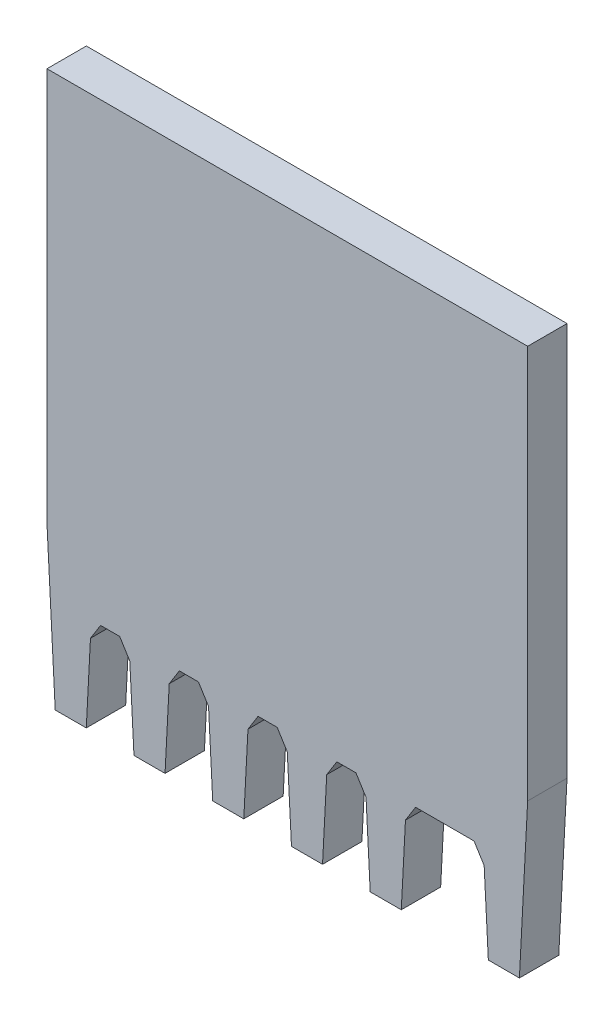
SolidWorks part; units mm, degrees
ref_plane "Front Plane" through (0, 0, 0) normal (0, 0, 1) x (1, 0, 0)
ref_plane "Top Plane" through (0, 0, 0) normal (0, 1, 0) x (1, 0, 0)
ref_plane "Right Plane" through (0, 0, 0) normal (1, 0, 0) x (0, 0, -1)
sketch "Sketch1" plane through (0, 0, 0) normal (0, 0, 1) x (1, 0, 0)
  line L0 (0, 0) -> (0, 21) construction
  line L1 (0, 21) -> (18.3124, 21) construction
  line L2 (18.3124, 21) -> (18.3124, 0) construction
  line L3 (18.3124, 0) -> (0, 0) construction
  line L4 (0, 3) -> (18.3124, 3) construction
  line L5 (0, 6) -> (18.3124, 6) construction
  line L6 (0.9062, 6) -> (0.9062, 0) construction
  line L7 (3.9062, 6) -> (3.9062, 0) construction
  line L8 (6.9062, 6) -> (6.9062, 0) construction
  line L9 (9.9062, 6) -> (9.9062, 0) construction
  line L10 (12.9062, 6) -> (12.9062, 0) construction
  line L11 (17.4062, 6) -> (17.4062, 0) construction
  line L12 (0.9062, 3) -> (3.9062, 3) construction
  line L13 (3.9062, 3) -> (6.9062, 3) construction
  line L14 (6.9062, 3) -> (9.9062, 3) construction
  line L15 (9.9062, 3) -> (12.9062, 3) construction
  line L16 (12.9062, 3) -> (17.4062, 3) construction
  line L17 (0.9062, 3) -> (0, 3) construction
  line L18 (17.4062, 3) -> (18.3124, 3) construction
  line L19 (2.4062, 3) -> (2.4062, 0) construction
  line L20 (5.4062, 3) -> (5.4062, 0) construction
  line L21 (8.4062, 3) -> (8.4062, 0) construction
  line L22 (11.4062, 3) -> (11.4062, 0) construction
  line L23 (15.1562, 3) -> (15.1562, 0) construction
  line L24 (14.4062, 3.75) -> (15.9062, 3.75) construction
  line L25 (0, 6) -> (0.3144, 0)
  line L26 (0.3144, 0) -> (1.4979, 0)
  line L27 (1.4979, 0) -> (1.6572, 3.0393)
  line L28 (3.1552, 3.0393) -> (3.3144, 0)
  line L29 (3.3144, 0) -> (4.4979, 0)
  line L30 (4.4979, 0) -> (4.6572, 3.0393)
  line L31 (6.1552, 3.0393) -> (6.3144, 0)
  line L32 (6.3144, 0) -> (7.4979, 0)
  line L33 (7.4979, 0) -> (7.6572, 3.0393)
  line L34 (9.1552, 3.0393) -> (9.3144, 0)
  line L35 (9.3144, 0) -> (10.4979, 0)
  line L36 (10.4979, 0) -> (10.6572, 3.0393)
  line L37 (12.1552, 3.0393) -> (12.3144, 0)
  line L38 (12.3144, 0) -> (13.4979, 0)
  line L39 (13.4979, 0) -> (13.6572, 3.0393)
  line L40 (16.6552, 3.0393) -> (16.8144, 0)
  line L41 (16.8144, 0) -> (17.9979, 0)
  line L42 (17.9979, 0) -> (18.3124, 6)
  line L44 (1.6572, 3.0393) -> (2.0426, 3.656)
  line L45 (0, 6) -> (0, 21)
  line L46 (0, 21) -> (18.3124, 21)
  line L47 (18.3124, 21) -> (18.3124, 6)
  line L48 (9.1562, 21) -> (9.1562, 6) construction
  line L49 (2.0426, 3.656) -> (2.7698, 3.656)
  line L50 (2.7698, 3.656) -> (3.1552, 3.0393)
  line L51 (4.6572, 3.0393) -> (5.0426, 3.656)
  line L52 (5.0426, 3.656) -> (5.7698, 3.656)
  line L53 (5.7698, 3.656) -> (6.1552, 3.0393)
  line L54 (7.6572, 3.0393) -> (8.0426, 3.656)
  line L55 (8.0426, 3.656) -> (8.7698, 3.656)
  line L56 (8.7698, 3.656) -> (9.1552, 3.0393)
  line L57 (10.6572, 3.0393) -> (11.0426, 3.656)
  line L58 (11.0426, 3.656) -> (11.7698, 3.656)
  line L59 (11.7698, 3.656) -> (12.1552, 3.0393)
  line L60 (13.6572, 3.0393) -> (14.0426, 3.656)
  line L61 (14.0426, 3.656) -> (16.2698, 3.656)
  line L62 (16.2698, 3.656) -> (16.6552, 3.0393)
  arc A0 (3.1552, 3.0393) -> (1.6572, 3.0393) centre (2.4062, 3) ccw construction
  arc A1 (6.1552, 3.0393) -> (4.6572, 3.0393) centre (5.4062, 3) ccw construction
  arc A2 (9.1552, 3.0393) -> (7.6572, 3.0393) centre (8.4062, 3) ccw construction
  arc A3 (12.1552, 3.0393) -> (10.6572, 3.0393) centre (11.4062, 3) ccw construction
  arc A4 (13.6572, 3.0393) -> (14.4062, 3.75) centre (14.4062, 3) cw construction
  arc A5 (16.6552, 3.0393) -> (15.9062, 3.75) centre (15.9062, 3) ccw construction
  dimension "D7" = 0.75
  dimension "D1" = 3
  dimension "D2" = 6
  dimension "D3" = 15
  dimension "D4" = 3
  dimension "D6" = 4.5
  dimension "D8" = 3
  dimension "D9" = 18.3124
  dimension "D10" = 21
extrude "Boss-Extrude1" add sketch "Sketch1" along normal blind 1.5
sketch "Sketch3" plane through (0, 0, 0) normal (0, 0, 1) x (1, 0, 0)
  line L0 (-0.4005, 6) -> (18.7129, 6)
  line L1 (18.7129, 3) -> (-0.4005, 3) construction
  line L2 (-0.4005, 0) -> (18.7129, 0) construction
  line L3 (-0.4005, -0.5) -> (18.7129, -0.5) construction
  line L4 (18.7129, -0.5) -> (18.7129, 6) construction
  line L5 (-0.4005, 6) -> (-0.4005, -0.5) construction
  line L6 (18.3124, 0) -> (0, 0) construction
  line L7 (0, 3) -> (18.3124, 3) construction
  line L8 (0, 6) -> (18.3124, 6) construction
  line L9 (0.3407, -0.5) -> (0, 6) construction
  line L10 (18.3124, 6) -> (17.9717, -0.5) construction
  line L11 (17.9979, 0) -> (18.3124, 6) construction
  line L12 (0, 6) -> (0.3144, 0) construction
  line L13 (5.4062, 6) -> (5.4062, -0.5) construction
  line L14 (3.9062, 6) -> (3.9062, -0.5) construction
  line L15 (5.4062, 3) -> (5.4062, 0) construction
  line L16 (3.1572, 3) -> (3.3407, -0.5) construction
  line L17 (2.7567, 3) -> (2.9401, -0.5)
  line L18 (3.1552, 3.0393) -> (3.3144, 0) construction
  line L19 (2.9401, -0.5) -> (4.8723, -0.5)
  line L20 (4.8723, -0.5) -> (5.0557, 3)
  line L21 (2.8484, 1.25) -> (3.2478, 1.2709) construction
  line L22 (5.9401, -0.5) -> (5.7567, 3)
  line L26 (7.8723, -0.5) -> (5.9401, -0.5)
  line L27 (8.0557, 3) -> (7.8723, -0.5)
  line L30 (2.4062, -0.5) -> (2.4062, 6) construction
  line L31 (2.4062, 3) -> (2.4062, 0) construction
  line L32 (8.4062, 6) -> (8.4062, -0.5) construction
  line L34 (11.4062, -0.5) -> (11.4062, 6) construction
  line L35 (15.1562, -0.5) -> (15.1562, 6) construction
  line L36 (8.4062, 3) -> (8.4062, 0) construction
  line L37 (11.4062, 3) -> (11.4062, 0) construction
  line L38 (15.1562, 3) -> (15.1562, 0) construction
  line L39 (10.8723, -0.5) -> (11.0557, 3)
  line L40 (8.9401, -0.5) -> (10.8723, -0.5)
  line L41 (8.7567, 3) -> (8.9401, -0.5)
  line L42 (11.9401, -0.5) -> (11.7567, 3)
  line L43 (13.8723, -0.5) -> (11.9401, -0.5)
  line L44 (14.0557, 3) -> (13.8723, -0.5)
  line L45 (16.4401, -0.5) -> (18.3723, -0.5)
  line L46 (16.2567, 3) -> (16.4401, -0.5)
  line L47 (18.3723, -0.5) -> (18.7129, 6)
  line L48 (1.8723, -0.5) -> (-0.0599, -0.5)
  line L49 (2.0557, 3) -> (1.8723, -0.5)
  line L50 (-0.0599, -0.5) -> (-0.4005, 6)
  line L51 (16.2567, 3) -> (14.0557, 3)
  line L52 (11.7567, 3) -> (11.0557, 3)
  line L53 (8.7567, 3) -> (8.0557, 3)
  line L54 (5.7567, 3) -> (5.0557, 3)
  line L55 (2.7567, 3) -> (2.0557, 3)
  dimension "D1" = 0.5
  dimension "D2" = 0.4
ref_plane "Plane1" through (3.9062, 0, 0) normal (1, 0, 0) x (0, 0, -1)
sketch "Sketch4" plane through (3.9062, 0, 0) normal (1, 0, 0) x (0, 0, -1)
  line L0 (0, 6) -> (0, -0.5) construction
  line L1 (0.6, 6) -> (-2.1, 6) construction
  line L2 (0.6, 6) -> (0.6, -0.5) construction
  line L3 (0.6, -0.5) -> (-2.1, -0.5) construction
  line L4 (-2.1, 6) -> (-2.1, -0.5) construction
  line L5 (-0.75, -0.5) -> (-0.75, 6) construction
  line L6 (-1.5, 6) -> (-1.5, -0.5) construction
  line L7 (0.6, 2.4005) -> (-2.1, 2.4005) construction
  line L8 (0.3, 6) -> (0.3, -0.5) construction
  line L9 (0.6, 2.4005) -> (3.846, 6) construction
  line L10 (2.2302, 6) -> (0.6, 4.1923) construction
  line L11 (0.6, 4.1923) -> (1.7139, 3.1878) construction
  line L12 (1.7139, 3.1878) -> (4.25, 6)
  line L13 (4.25, 6) -> (0.6, 6) construction
  line L14 (0.3, 1) -> (-1.8, 1) construction
  line L15 (-2.1, 0) -> (0.6, 0) construction
  line L16 (1.7139, 3.1878) -> (1.4912, 3.3887)
  line L17 (1.4912, 3.3887) -> (0.6, 2.4005)
  line L18 (-3.2139, 3.1878) -> (-5.75, 6)
  line L19 (-3.2139, 3.1878) -> (-2.9912, 3.3887)
  line L20 (-2.9912, 3.3887) -> (-2.1, 2.4005)
  line L21 (-2.1, 6) -> (-5.75, 6) construction
  line L22 (0.6, 3.0724) -> (3.2401, 6) construction
  arc A0 (0.4965, 2.2224) -> (0.6, -0.5) centre (4.2, 1) ccw
  arc A1 (0.6, 2.4005) -> (0.4965, 2.2224) centre (0.9713, 2.0656) ccw
  arc A2 (-2.1, 2.4005) -> (-1.9965, 2.2224) centre (-2.4713, 2.0656) cw
  arc A3 (-1.9965, 2.2224) -> (-2.1, -0.5) centre (-5.7, 1) cw
  dimension "D6" = 0.5
  dimension "D1" = 0.6
  dimension "D2" = 0.3
  dimension "D3" = 1.5
  dimension "D4" = 1
  dimension "D5" = 0.3
  dimension "D7" = 10
sketch "Sketch5" plane through (0, 0, 0) normal (1, 0, 0) x (0, 0, -1)
  line L0 (2.2302, 6) -> (0.6, 4.1923) construction
  line L1 (0.6, 4.1923) -> (1.7139, 3.1878) construction
  line L2 (1.7139, 3.1878) -> (4.25, 6) construction
  line L3 (2.2302, 6) -> (0.6, 4.1923) construction
  line L4 (0.6, 4.1923) -> (1.7139, 3.1878) construction
  line L5 (1.7139, 3.1878) -> (4.25, 6) construction
ref_plane "Plane2" through (0, 2.6105, -2.3541) normal (0, 0.7426, -0.6697) x (1, 0, 0)
sketch "Sketch6" plane through (0, 2.6105, -2.3541) normal (0, 0.7426, -0.6697) x (1, 0, 0)
  line L1 (3.9062, -2.362) -> (3.9062, -0.862) construction
  line L2 (3.9062, -2.362) -> (3.9062, -5.0612) construction
  line L3 (4.6562, -5.0612) -> (3.1562, -5.0612)
  line L4 (4.6562, -1.612) -> (3.1562, -1.612) construction
  line L5 (3.1562, -1.612) -> (3.1562, -5.0612)
  line L6 (4.6562, -1.612) -> (4.6562, -5.0612)
  line L10 (2.4062, -5.0612) -> (15.1562, -5.0612) construction
  line L11 (15.1562, -5.0612) -> (15.1562, -0.862) construction
  line L12 (15.1562, -0.862) -> (2.4062, -0.862) construction
  line L13 (2.4062, -0.862) -> (2.4062, -5.0612) construction
  line L14 (15.1562, 0.3349) -> (15.1562, -4.0182) construction
  line L15 (2.4062, 0.3349) -> (2.4062, -4.0182) construction
  line L16 (11.4062, -5.0612) -> (11.4062, -0.862) construction
  line L17 (8.4062, -5.0612) -> (8.4062, -0.862) construction
  line L18 (5.4062, -5.0612) -> (5.4062, -0.862) construction
  line L19 (5.4062, -4.0182) -> (5.4062, 0.3349) construction
  line L20 (8.4062, -4.0182) -> (8.4062, 0.3349) construction
  line L21 (11.4062, 0.3349) -> (11.4062, -4.0182) construction
  line L22 (0.1562, -1.612) -> (0.1562, -5.0612)
  line L23 (0.1562, -5.0612) -> (1.6562, -5.0612)
  line L24 (1.6562, -1.612) -> (1.6562, -5.0612)
  line L25 (7.6562, -1.612) -> (7.6562, -5.0612)
  line L26 (6.1562, -5.0612) -> (7.6562, -5.0612)
  line L27 (6.1562, -1.612) -> (6.1562, -5.0612)
  line L28 (10.6562, -1.612) -> (10.6562, -5.0612)
  line L29 (10.6562, -5.0612) -> (9.1562, -5.0612)
  line L30 (9.1562, -1.612) -> (9.1562, -5.0612)
  line L31 (13.6562, -1.612) -> (13.6562, -5.0612)
  line L32 (12.1562, -5.0612) -> (13.6562, -5.0612)
  line L33 (12.1562, -1.612) -> (12.1562, -5.0612)
  line L34 (18.1562, -1.612) -> (18.1562, -5.0612)
  line L35 (18.1562, -5.0612) -> (16.6562, -5.0612)
  line L36 (16.6562, -1.612) -> (16.6562, -5.0612)
  circle A0 centre (3.9062, -1.612) radius 0.75 construction
  arc A1 (4.6562, -1.612) -> (3.1562, -1.612) centre (3.9062, -1.612) ccw
  arc A2 (0.1562, -1.612) -> (1.6562, -1.612) centre (0.9062, -1.612) cw
  arc A3 (6.1562, -1.612) -> (7.6562, -1.612) centre (6.9062, -1.612) cw
  arc A4 (10.6562, -1.612) -> (9.1562, -1.612) centre (9.9062, -1.612) ccw
  arc A5 (12.1562, -1.612) -> (13.6562, -1.612) centre (12.9062, -1.612) cw
  arc A6 (18.1562, -1.612) -> (16.6562, -1.612) centre (17.4062, -1.612) ccw
ref_plane "Plane3" through (0, 1.6223, -1.463) normal (0, 0.7426, -0.6697) x (1, 0, 0)
sketch "Sketch7" plane through (0, 1.6223, -1.463) normal (0, 0.7426, -0.6697) x (1, 0, 0)
  line L0 (3.1562, -1.612) -> (3.1562, -5.0612) construction
  line L1 (4.6562, -5.0612) -> (3.1562, -5.0612) construction
  line L2 (4.6562, -1.612) -> (4.6562, -5.0612) construction
  line L3 (3.1562, -1.612) -> (3.1562, -5.0612) construction
  line L4 (4.6562, -5.0612) -> (3.1562, -5.0612) construction
  line L5 (4.6562, -1.612) -> (4.6562, -5.0612) construction
  line L6 (3.9062, -0.862) -> (3.9062, -5.0612) construction
  line L7 (4.6562, -1.612) -> (3.1562, -1.612) construction
  line L8 (4.6562, -2.362) -> (3.1562, -2.362) construction
  line L9 (3.4562, -1.612) -> (3.4562, -2.362)
  line L10 (3.4562, -2.362) -> (4.3562, -2.362)
  line L11 (4.3562, -2.362) -> (4.3562, -1.612)
  line L12 (2.4062, -0.862) -> (2.4062, -5.0612) construction
  line L13 (2.4062, -5.0612) -> (15.1562, -5.0612) construction
  line L14 (15.1562, -0.862) -> (2.4062, -0.862) construction
  line L15 (5.4062, -5.0612) -> (5.4062, -0.862) construction
  line L16 (8.4062, -5.0612) -> (8.4062, -0.862) construction
  line L17 (11.4062, -5.0612) -> (11.4062, -0.862) construction
  line L18 (15.1562, -5.0612) -> (15.1562, -0.862) construction
  line L19 (2.4062, -0.862) -> (2.4062, -5.0612) construction
  line L20 (2.4062, -5.0612) -> (15.1562, -5.0612) construction
  line L21 (15.1562, -0.862) -> (2.4062, -0.862) construction
  line L22 (5.4062, -5.0612) -> (5.4062, -0.862) construction
  line L23 (8.4062, -5.0612) -> (8.4062, -0.862) construction
  line L24 (11.4062, -5.0612) -> (11.4062, -0.862) construction
  line L25 (15.1562, -5.0612) -> (15.1562, -0.862) construction
  line L26 (0.4562, -2.362) -> (0.4562, -1.612)
  line L27 (1.3562, -2.362) -> (0.4562, -2.362)
  line L28 (1.3562, -1.612) -> (1.3562, -2.362)
  line L29 (7.3562, -2.362) -> (6.4562, -2.362)
  line L30 (7.3562, -1.612) -> (7.3562, -2.362)
  line L31 (6.4562, -2.362) -> (6.4562, -1.612)
  line L32 (9.4562, -1.612) -> (9.4562, -2.362)
  line L33 (10.3562, -2.362) -> (10.3562, -1.612)
  line L34 (9.4562, -2.362) -> (10.3562, -2.362)
  line L35 (13.3562, -1.612) -> (13.3562, -2.362)
  line L36 (12.4562, -2.362) -> (12.4562, -1.612)
  line L37 (13.3562, -2.362) -> (12.4562, -2.362)
  line L38 (16.9562, -1.612) -> (16.9562, -2.362)
  line L39 (17.8562, -2.362) -> (17.8562, -1.612)
  line L40 (16.9562, -2.362) -> (17.8562, -2.362)
  arc A0 (4.6562, -1.612) -> (3.1562, -1.612) centre (3.9062, -1.612) ccw construction
  arc A1 (4.6562, -1.612) -> (3.1562, -1.612) centre (3.9062, -1.612) ccw construction
  circle A2 centre (3.9062, -1.612) radius 0.45 construction
  arc A3 (4.3562, -1.612) -> (3.4562, -1.612) centre (3.9062, -1.612) ccw
  arc A4 (0.4562, -1.612) -> (1.3562, -1.612) centre (0.9062, -1.612) cw
  arc A5 (6.4562, -1.612) -> (7.3562, -1.612) centre (6.9062, -1.612) cw
  arc A6 (10.3562, -1.612) -> (9.4562, -1.612) centre (9.9062, -1.612) ccw
  arc A7 (12.4562, -1.612) -> (13.3562, -1.612) centre (12.9062, -1.612) cw
  arc A8 (17.8562, -1.612) -> (16.9562, -1.612) centre (17.4062, -1.612) ccw
ref_plane "bisect" through (0, 0, 0.75) normal (0, 0, 1) x (1, 0, 0)
ref_plane "insert_surface" through (0, 6, 0) normal (0, 1, 0) x (1, 0, 0)
sketch "Sketch8" plane through (0, 6, 0) normal (0, 1, 0) x (1, 0, 0)
  line L0 (18.7129, -0.75) -> (-0.4005, -0.75) construction
  line L1 (-0.4005, 0.6) -> (18.7129, 0.6)
  line L2 (-0.4005, 0.6) -> (-0.4005, -2.1)
  line L3 (-0.4005, -2.1) -> (18.7129, -2.1)
  line L4 (18.7129, 0.6) -> (18.7129, -2.1)
  line L5 (9.1562, 0.6) -> (9.1562, -2.1) construction
  line L6 (0, 0) -> (18.3124, 0) construction
  line L7 (0, 0) -> (0, -1.5) construction
  line L8 (0, -1.5) -> (18.3124, -1.5) construction
  line L9 (18.3124, 0) -> (18.3124, -1.5) construction
  line L10 (18.7129, 0.3) -> (-0.4005, 0.3) construction
  line L11 (18.7129, -1.8) -> (-0.4005, -1.8) construction
sketch "Sketch9" plane through (0, 0, 0) normal (0, 0, 1) x (1, 0, 0)
  line L0 (18.3723, -0.5) -> (18.7129, 6) construction
  line L1 (-0.4005, 6) -> (18.7129, 6) construction
  line L2 (-0.0599, -0.5) -> (-0.4005, 6) construction
  line L3 (1.8723, -0.5) -> (-0.0599, -0.5) construction
  line L4 (2.0557, 3) -> (1.8723, -0.5) construction
  line L5 (2.7567, 3) -> (2.0557, 3) construction
  line L6 (2.7567, 3) -> (2.9401, -0.5) construction
  line L7 (2.9401, -0.5) -> (4.8723, -0.5) construction
  line L8 (4.8723, -0.5) -> (5.0557, 3) construction
  line L9 (5.7567, 3) -> (5.0557, 3) construction
  line L10 (5.9401, -0.5) -> (5.7567, 3) construction
  line L11 (7.8723, -0.5) -> (5.9401, -0.5) construction
  line L12 (8.0557, 3) -> (7.8723, -0.5) construction
  line L13 (8.7567, 3) -> (8.0557, 3) construction
  line L14 (8.7567, 3) -> (8.9401, -0.5) construction
  line L15 (8.9401, -0.5) -> (10.8723, -0.5) construction
  line L16 (10.8723, -0.5) -> (11.0557, 3) construction
  line L17 (11.7567, 3) -> (11.0557, 3) construction
  line L18 (11.9401, -0.5) -> (11.7567, 3) construction
  line L19 (13.8723, -0.5) -> (11.9401, -0.5) construction
  line L20 (14.0557, 3) -> (13.8723, -0.5) construction
  line L21 (16.2567, 3) -> (14.0557, 3) construction
  line L22 (16.2567, 3) -> (16.4401, -0.5) construction
  line L23 (16.4401, -0.5) -> (18.3723, -0.5) construction
  line L24 (18.3723, -0.5) -> (18.7129, 6)
  line L25 (-0.4005, 6) -> (18.7129, 6) construction
  line L26 (-0.0599, -0.5) -> (-0.4005, 6)
  line L27 (1.8723, -0.5) -> (-0.0599, -0.5)
  line L28 (2.0557, 3) -> (1.8723, -0.5)
  line L29 (2.7567, 3) -> (2.0557, 3) construction
  line L30 (2.7567, 3) -> (2.9401, -0.5)
  line L31 (2.9401, -0.5) -> (4.8723, -0.5)
  line L32 (4.8723, -0.5) -> (5.0557, 3)
  line L33 (5.7567, 3) -> (5.0557, 3) construction
  line L34 (5.9401, -0.5) -> (5.7567, 3)
  line L35 (7.8723, -0.5) -> (5.9401, -0.5)
  line L36 (8.0557, 3) -> (7.8723, -0.5)
  line L37 (8.7567, 3) -> (8.0557, 3) construction
  line L38 (8.7567, 3) -> (8.9401, -0.5)
  line L39 (8.9401, -0.5) -> (10.8723, -0.5)
  line L40 (10.8723, -0.5) -> (11.0557, 3)
  line L41 (11.7567, 3) -> (11.0557, 3) construction
  line L42 (11.9401, -0.5) -> (11.7567, 3)
  line L43 (13.8723, -0.5) -> (11.9401, -0.5)
  line L44 (14.0557, 3) -> (13.8723, -0.5)
  line L45 (16.2567, 3) -> (14.0557, 3) construction
  line L46 (16.2567, 3) -> (16.4401, -0.5)
  line L47 (16.4401, -0.5) -> (18.3723, -0.5)
  line L48 (16.2567, 3) -> (16.2567, 6)
  line L49 (14.0557, 3) -> (14.0557, 6)
  line L50 (11.7567, 3) -> (11.7567, 6)
  line L51 (18.7129, 6) -> (-0.4005, 6) construction
  line L52 (11.0557, 3) -> (11.0557, 6)
  line L53 (-0.4005, 6) -> (18.7129, 6) construction
  line L54 (8.7567, 3) -> (8.7567, 6)
  line L55 (8.0557, 3) -> (8.0557, 6)
  line L58 (5.7567, 3) -> (5.7567, 6)
  line L60 (5.0557, 3) -> (5.0557, 6)
  line L62 (15.1562, -0.5) -> (15.1562, 6) construction
  line L63 (15.1562, -0.5) -> (15.1562, 6) construction
  line L64 (2.7567, 3) -> (2.7567, 6)
  line L65 (2.0557, 3) -> (2.0557, 6)
  line L67 (18.7129, 6) -> (16.2567, 6)
  line L68 (14.0557, 6) -> (11.7567, 6)
  line L69 (11.0557, 6) -> (8.7567, 6)
  line L70 (8.0557, 6) -> (5.7567, 6)
  line L71 (5.0557, 6) -> (2.7567, 6)
  line L72 (2.0557, 6) -> (-0.4005, 6)
sketch "rgb_led" plane through (0, 0, 1.5) normal (0, 0, 1) x (1, 0, 0)
  line L0 (18.3124, 18) -> (0, 18) construction
  line L1 (18.3124, 6) -> (18.3124, 21) construction
  line L2 (0, 21) -> (0, 6) construction
  line L3 (9.1562, 21) -> (9.1562, 18) construction
  line L4 (18.3124, 21) -> (0, 21) construction
  line L6 (12.0562, 19.8) -> (6.2562, 19.8)
  line L7 (12.0562, 19.8) -> (12.0562, 16.2)
  line L8 (12.0562, 16.2) -> (6.2562, 16.2)
  line L9 (6.2562, 19.8) -> (6.2562, 16.2)
  dimension "D1" = 3
  dimension "D2" = 3.6
  dimension "D3" = 5.8
